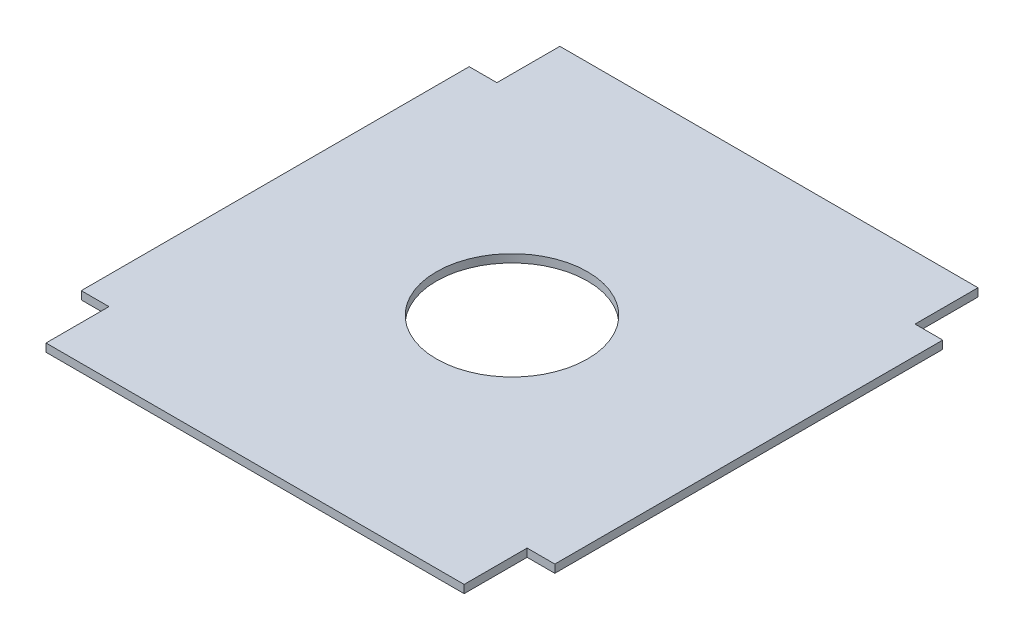
SolidWorks part; units mm, degrees
ref_plane "Front Plane" through (0, 0, 0) normal (0, 0, 1) x (1, 0, 0)
ref_plane "Top Plane" through (0, 0, 0) normal (0, 1, 0) x (1, 0, 0)
ref_plane "Right Plane" through (0, 0, 0) normal (1, 0, 0) x (0, 0, -1)
sketch "Sketch1" plane through (0, 0, 0) normal (0, 1, 0) x (1, 0, 0)
  line L5 (-41.5, -38.5) -> (41.5, 38.5) construction
  line L6 (-41.5, 38.5) -> (41.5, -38.5) construction
  line L8 (-41.5, 38.5) -> (-41.5, 51)
  line L9 (-41.5, 51) -> (41.5, 51)
  line L10 (41.5, 38.5) -> (41.5, 51)
  line L12 (-41.5, -38.5) -> (-41.5, -51)
  line L13 (-41.5, -51) -> (41.5, -51)
  line L14 (41.5, -38.5) -> (41.5, -51)
  line L15 (-41.5, 38.5) -> (-47, 38.5)
  line L17 (-41.5, -38.5) -> (-47, -38.5)
  line L18 (-47, 38.5) -> (-47, -38.5)
  line L19 (41.5, 38.5) -> (47, 38.5)
  line L21 (41.5, -38.5) -> (47, -38.5)
  line L22 (47, 38.5) -> (47, -38.5)
  point P0 (0, 0)
  dimension "D1" = 83
  dimension "D2" = 77
  dimension "D3" = 5.5
  dimension "D4" = 12.5
extrude "Boss-Extrude1" add sketch "Sketch1" along normal blind 1.6
sketch "Sketch2" plane through (0, 1.6, 0) normal (0, 1, 0) x (1, 0, 0)
  circle A0 centre (0, 0) radius 15
  dimension "D1" = 30
extrude "Cut-Extrude1" cut sketch "Sketch2" against normal blind 1.6
